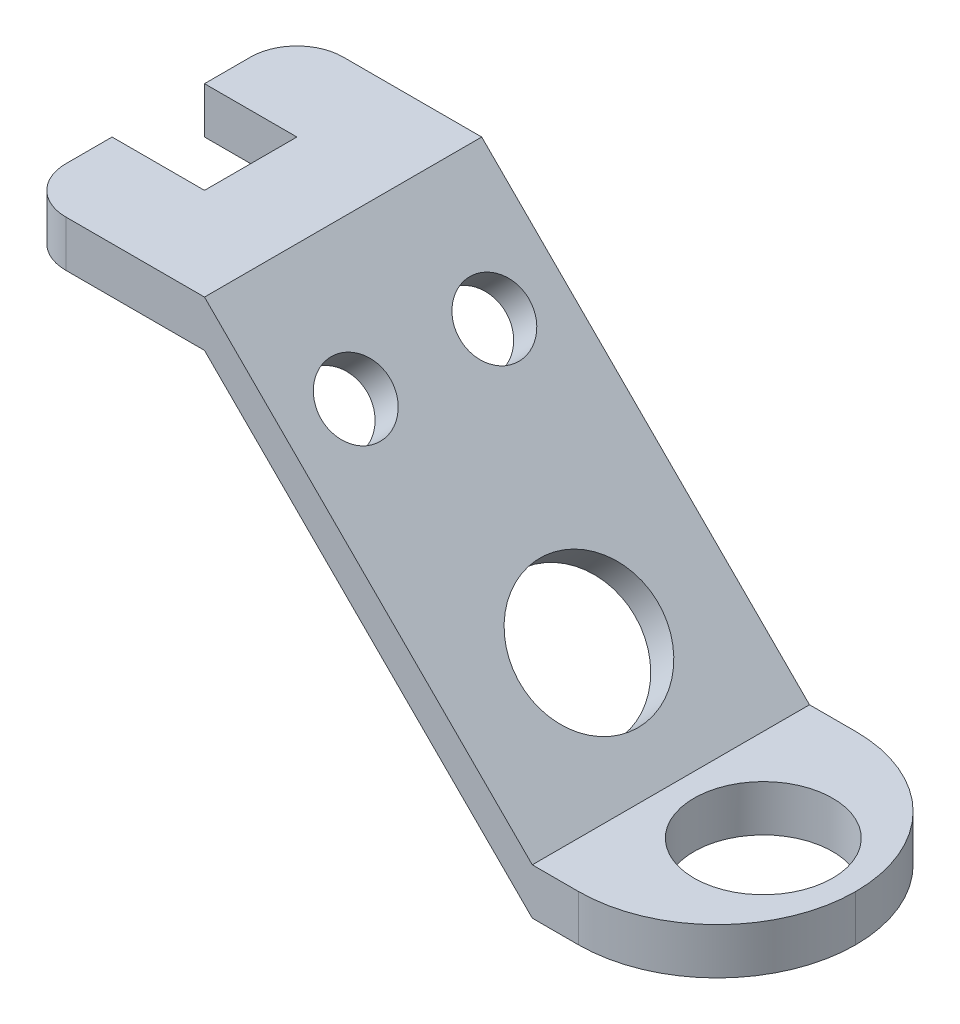
SolidWorks part; units mm, degrees
ref_plane "Alzado" through (0, 0, 0) normal (0, 0, 1) x (1, 0, 0)
ref_plane "Planta" through (0, 0, 0) normal (0, 1, 0) x (1, 0, 0)
ref_plane "Vista lateral" through (0, 0, 0) normal (1, 0, 0) x (0, 0, -1)
sketch "Croquis2" plane through (0, 0, 0) normal (0, 0, 1) x (1, 0, 0)
  line L0 (-36.1801, 22.9071) -> (3.8199, 22.9071)
  line L1 (-36.1801, 22.9071) -> (-36.1801, 32.9071)
  line L2 (-36.1801, 32.9071) -> (3.8199, 32.9071)
  line L3 (3.8199, 22.9071) -> (74.7678, -48.0408)
  line L4 (3.8199, 32.9071) -> (74.7678, -38.0408)
  line L5 (74.7678, -38.0408) -> (114.7678, -38.0408)
  line L6 (114.7678, -38.0408) -> (114.7678, -48.0408)
  line L7 (114.7678, -48.0408) -> (74.7678, -48.0408)
  dimension "D1" = 225
  dimension "D2" = 40
  dimension "D3" = 40
  dimension "D4" = 10
  dimension "D5" = 40
  dimension "D6" = 40
  dimension "D7" = 225
extrude "Saliente-Extruir1" add sketch "Croquis2" along normal blind 60
sketch "Croquis3" plane through (0, 0, 0) normal (0, 1, 0) x (1, 0, 0)
  line L0 (-36.1801, -60) -> (-36.1801, 0) construction
  line L1 (-56.1801, -40) -> (-16.1801, -40)
  line L2 (-56.1801, -40) -> (-56.1801, -20)
  line L3 (-56.1801, -20) -> (-16.1801, -20)
  line L4 (-16.1801, -40) -> (-16.1801, -20)
  line L5 (-56.1801, -40) -> (-16.1801, -20) construction
  line L6 (-56.1801, -20) -> (-16.1801, -40) construction
  point P0 (-36.1801, -30)
extrude "Cortar-Extruir1" cut sketch "Croquis3" along normal blind 46
sketch "Croquis4" plane through (0, 0, 0) normal (0, 1, 0) x (1, 0, 0)
  circle A0 centre (94.7678, -30) radius 15
extrude "Cortar-Extruir5" cut sketch "Croquis4" against normal blind 57
sketch "Croquis12" plane through (18.3635, 18.3635, 0) normal (0.7071, 0.7071, 0) x (0, 0, -1)
  circle A0 centre (-15, -4.5161) radius 7.5
  circle A1 centre (-45, -4.5161) radius 7.5
  circle A2 centre (-30, -54.6839) radius 15
extrude "Cortar-Extruir6" cut sketch "Croquis12" against normal blind 19 and the other way blind 16
fillet "Redondeo2" radius 10 2 edges at (-36.1801, 27.9071, 0) (-36.1801, 27.9071, 60)
fillet "Redondeo3" radius 30 2 edges at (114.7678, -43.0408, 60) (114.7678, -43.0408, 0)
